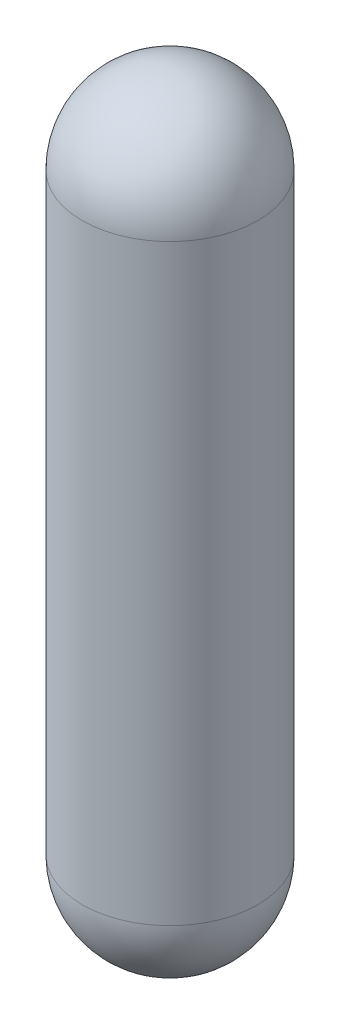
SolidWorks part; units mm, degrees
other "Markup1"
sketch "Sketch2" plane through (-160, -160, 160) normal (0, 0, 1) x (1, 0, 0)
material "Titanium"
ref_plane "Front Plane" through (0, 0, 0) normal (0, 0, 1) x (1, 0, 0)
ref_plane "Top Plane" through (0, 0, 0) normal (0, 1, 0) x (1, 0, 0)
ref_plane "Right Plane" through (0, 0, 0) normal (1, 0, 0) x (0, 0, -1)
sketch "Sketch1" plane through (0, 0, 0) normal (0, 0, 1) x (1, 0, 0)
  line L0 (0, 1542.8) -> (0, 1771.4)
  line L2 (0, 0) -> (0, 1542.8)
  line L4 (228.6, 0) -> (228.6, 1542.8)
  line L5 (0, 0) -> (0, -228.6)
  line L6 (0, 738.4774) -> (228.6, 738.4774) construction
  arc A0 (0, -228.6) -> (228.6, 0) centre (0, 0) ccw
  arc A1 (228.6, 1542.8) -> (0, 1771.4) centre (0, 1542.8) ccw
  dimension "D1" = 228.6
  dimension "D2" = 2000
revolve "Revolve1" add sketch "Sketch1" angle 360 about L2
